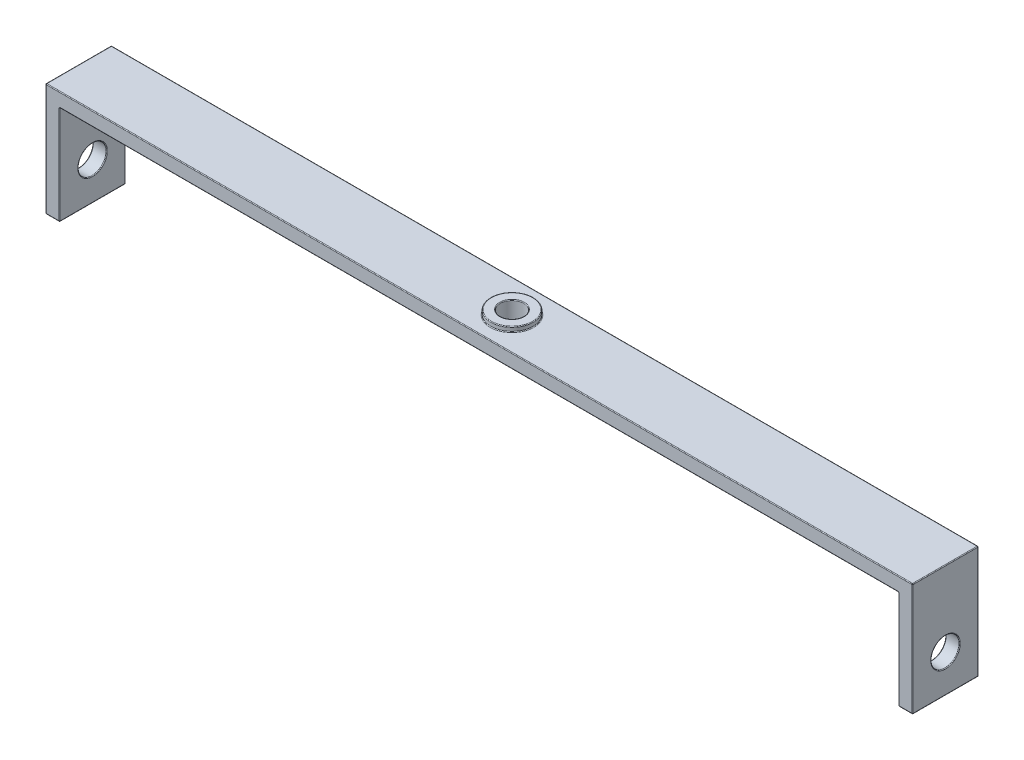
SolidWorks part; units mm, degrees
ref_plane "Front Plane" through (0, 0, 0) normal (0, 0, 1) x (1, 0, 0)
ref_plane "Top Plane" through (0, 0, 0) normal (0, 1, 0) x (1, 0, 0)
ref_plane "Right Plane" through (0, 0, 0) normal (1, 0, 0) x (0, 0, -1)
sketch "Sketch2" plane through (0, 0, 0) normal (0, 0, 1) x (1, 0, 0)
  line L0 (-46.11, 0) -> (46.11, 0)
  line L1 (46.11, 0) -> (46.11, -12)
  line L2 (-46.11, 0) -> (-46.11, -12)
  line L3 (44.61, -1.5) -> (44.61, -12)
  line L4 (-44.61, -1.5) -> (44.61, -1.5)
  line L5 (-44.61, -1.5) -> (-44.61, -12)
  line L6 (-46.11, -12) -> (-44.61, -12)
  line L7 (44.61, -12) -> (46.11, -12)
  point P2 (0, 0)
  dimension "D1" = 92.22
  dimension "D2" = 12
  dimension "D3" = 1.5
extrude "Boss-Extrude1" add sketch "Sketch2" along normal blind 3.5 and the other way blind 3.5
sketch "Sketch3" plane through (0, 0, 0) normal (0, 1, 0) x (1, 0, 0)
  circle A0 centre (0, 0) radius 1.25
  dimension "D1" = 2.5
extrude "Cut-Extrude1" cut sketch "Sketch3" against normal up to surface (1.5 mm away) up to face at (0, -1.5, 0)
sketch "Sketch9" plane through (0, 0, 0) normal (0, 1, 0) x (1, 0, 0)
  circle A0 centre (0, 0) radius 1.25 construction
  circle A1 centre (0, 0) radius 1.25
  circle A2 centre (0, 0) radius 2.25
  dimension "D1" = 1
extrude "Boss-Extrude5" add sketch "Sketch9" along normal blind 0.5
sketch "Sketch11" plane through (0, 0, 0) normal (1, 0, 0) x (0, 0, -1)
  line L0 (0, 0.5) -> (0, -8) construction
  line L1 (2.25, 0.5) -> (-2.25, 0.5) construction
  circle A0 centre (0, -8) radius 1.5
  dimension "D1" = 3
  dimension "D2" = 8.5
extrude "Cut-Extrude2" cut sketch "Sketch11" along normal up to surface and the other way up to surface up to face at (46.11, -6, 0) other way up to face at (-46.11, -6, 0)
fillet "Fillet1" radius 0.075 32 edges at (-46.11, -8, 1.5) (46.11, -8, -1.5) (-44.61, -8, -1.5) (44.61, -8, 1.5) (-1.25, 0.5, 0) (-2.25, 0, 0) (-2.25, 0.5, 0) (0, -1.5, -1.25) (-46.11, -6, 3.5) (-45.36, -12, 3.5) (-44.61, -6.75, 3.5) (0, -1.5, 3.5) (44.61, -6.75, 3.5) (45.36, -12, 3.5) (46.11, -6, 3.5) (-46.11, -6, -3.5) (-45.36, -12, -3.5) (-44.61, -6.75, -3.5) (0, -1.5, -3.5) (44.61, -6.75, -3.5) (45.36, -12, -3.5) (46.11, -6, -3.5) (0, 0, -3.5) (-46.11, -12, 0) (-44.61, -12, 0) (-44.61, -1.5, 0) (44.61, -1.5, 0) (44.61, -12, 0) (46.11, -12, 0) (46.11, 0, 0) (-46.11, 0, 0) (0, 0, 3.5)
